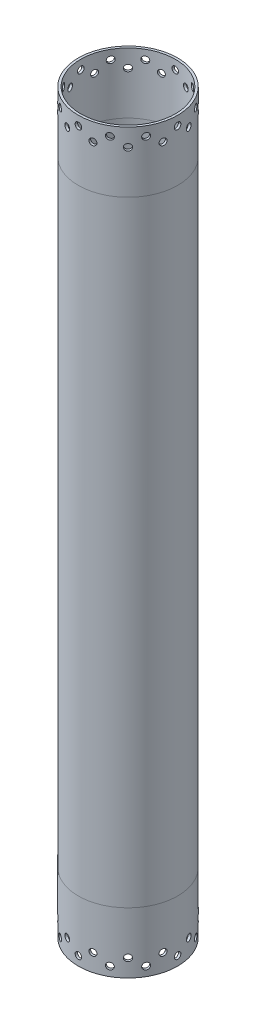
SolidWorks part; units mm, degrees
material "6061-T6 (SS)"
ref_plane "Front Plane" through (0, 0, 0) normal (0, 0, 1) x (1, 0, 0)
ref_plane "Top Plane" through (0, 0, 0) normal (0, 1, 0) x (1, 0, 0)
ref_plane "Right Plane" through (0, 0, 0) normal (1, 0, 0) x (0, 0, -1)
sketch "Sketch2" plane through (0, 0, 0) normal (0, 1, 0) x (1, 0, 0)
  circle A0 centre (0, 0) radius 76.2
  circle A1 centre (0, 0) radius 72.5932
  dimension "D1" = 152.4
  dimension "D2" = 145.1864
extrude "Boss-Extrude1" add sketch "Sketch2" along normal blind 1130.3
sketch "Sketch3" plane through (0, 0, 0) normal (0, 0, 1) x (1, 0, 0)
  line L0 (0, 1130.3) -> (0, 1116.203) construction
  line L1 (72.5932, 1130.3) -> (-72.5932, 1130.3) construction
  circle A0 centre (0, 1116.203) radius 5.0419
  dimension "D1" = 10.0838
  dimension "D2" = 14.097
extrude "Cut-Extrude1" cut sketch "Sketch3" against normal blind 1143
ref_plane "Plane1" through (-19.722, 0, 73.6035) normal (-0.2588, 0, 0.9659) x (0, -1, 0)
sketch "Sketch6" plane through (-19.722, 0, 73.6035) normal (-0.2588, 0, 0.9659) x (0, -1, 0)
  line L0 (-1130.3, 0) -> (-1103.503, 0) construction
  line L1 (-1130.3, 76.2) -> (-1130.3, -76.2) construction
  circle A0 centre (-1103.503, 0) radius 5.0419
  dimension "D1" = 10.0838
  dimension "D2" = 26.797
extrude "Cut-Extrude2" cut sketch "Sketch6" against normal blind 25.4
pattern_circular "CirPattern2" count 12 over 360 about axis through (0, 1130.3, 0) along (0, -1, 0) of "Cut-Extrude2", "Cut-Extrude1"
ref_plane "Plane2" through (0, 565.15, 0) normal (0, 1, 0) x (1, 0, 0)
mirror "Mirror1" about plane through (0, 565.15, 0) normal (0, 1, 0) of "CirPattern2"
ref_plane "Plane3" through (0, 93.218, 0) normal (0, -1, 0) x (-1, 0, 0)
ref_plane "Plane4" through (0, 1037.082, 0) normal (0, 1, 0) x (1, 0, 0)
split line "Split Line1"
split line "Split Line2"
ref_axis "Axis1" through (-52.4018, 1103.503, 52.4018) along (-0.7071, 0, 0.7071)
ref_axis "Axis2" through (-18.7398, 1103.503, 69.9379) along (-0.2588, 0, 0.9659)
ref_plane "Plane5" through (0, 1103.503, 0) normal (0, -1, 0) x (-1, 0, 0)
ref_axis "Axis3" through (-37.6178, 1116.203, 65.1559) along (0.5, 0, -0.866)
ref_axis "Axis4" through (-65.1541, 1116.203, 37.6168) along (0.866, 0, -0.5)
ref_plane "Plane6" through (0, 1116.203, 0) normal (0, 1, 0) x (1, 0, 0)
ref_axis "Axis5" through (-37.6178, 14.097, 65.1559) along (0.5, 0, -0.866)
ref_axis "Axis6" through (0, 14.097, 76.2) along (0, 0, -1)
ref_axis "Axis7" through (-18.7398, 26.797, 69.9379) along (-0.2588, 0, 0.9659)
ref_axis "Axis8" through (-52.4018, 26.797, 52.4018) along (-0.7071, 0, 0.7071)
ref_plane "Plane7" through (0, 26.797, 0) normal (0, 1, 0) x (1, 0, 0)
ref_plane "Plane8" through (0, 14.097, 0) normal (0, 1, 0) x (1, 0, 0)
split line "Split Line3"
split line "Split Line4"
split line "Split Line5"
split line "Split Line6"
equation "\"holeDia\"=0.397"
equation "\"D1@Sketch3\"=\"holeDia\""
equation "\"D1@Sketch6\"=\"holeDia\""
equation "\"numHoles\"=12"
equation "\"D1@CirPattern2\"=\"numHoles\""
equation "\"D1@Plane1\"=180/\"numHoles\""
equation "\"D2@Sketch6\"=\"D2@Sketch3\"+0.5"
